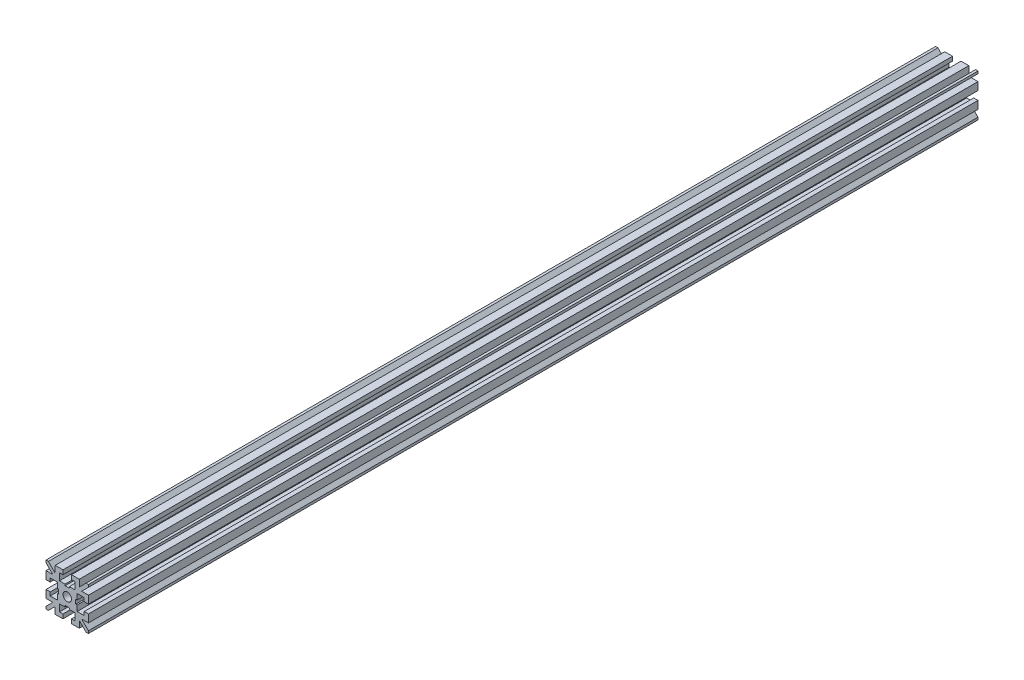
SolidWorks part; units mm, degrees
ref_plane "Front Plane" through (0, 0, 0) normal (0, 0, 1) x (1, 0, 0)
ref_plane "Top Plane" through (0, 0, 0) normal (0, 1, 0) x (1, 0, 0)
ref_plane "Right Plane" through (0, 0, 0) normal (1, 0, 0) x (0, 0, -1)
sketch "Sketch1" plane through (0, 0, 0) normal (0, 0, 1) x (1, 0, 0)
  line L1 (-9.0006, 3.7616) -> (5.9994, 3.7616)
  line L2 (-9.0006, 3.7616) -> (-9.0006, -11.2384)
  line L3 (-9.0006, -11.2384) -> (5.9994, -11.2384)
  line L4 (5.9994, 3.7616) -> (5.9994, -11.2384)
  dimension "D1" = 15
  dimension "D2" = 15
extrude "Boss-Extrude1" add sketch "Sketch1" along normal blind 314.19
sketch "Sketch2" plane through (0, 0, 314.19) normal (0, 0, 1) x (1, 0, 0)
  line L0 (-9.0006, 3.7616) -> (5.9994, -11.2384) construction
  line L1 (5.9994, 3.7616) -> (-9.0006, -11.2384) construction
  line L4 (1.9994, -4.4884) -> (1.9994, -6.4884)
  line L5 (5.9994, -3.7384) -> (1.9994, -3.7384) construction
  line L6 (5.9994, -11.2384) -> (5.9994, 3.7616) construction
  line L7 (-1.5006, 3.7616) -> (-1.5006, -3.7384) construction
  line L8 (5.9994, 3.7616) -> (-9.0006, 3.7616) construction
  line L9 (-9.0006, -3.7384) -> (-1.5006, -3.7384) construction
  line L10 (-9.0006, 3.7616) -> (-9.0006, -11.2384) construction
  line L11 (-1.5006, -11.2384) -> (-1.5006, -3.7384) construction
  line L12 (-9.0006, -11.2384) -> (5.9994, -11.2384) construction
  line L13 (1.9994, -4.4884) -> (1.4994, -4.4884)
  line L14 (1.9994, -0.9884) -> (4.4994, -0.9884)
  line L15 (1.9994, -0.9884) -> (1.9994, -2.9884)
  line L16 (1.9994, -6.4884) -> (4.4994, -6.4884)
  line L17 (4.4994, -0.9884) -> (4.4994, -6.4884)
  line L18 (-4.2506, -7.2384) -> (-4.2506, -9.7384)
  line L19 (1.9994, -2.9884) -> (1.4994, -2.9884)
  line L20 (1.4994, -4.4884) -> (1.4994, -2.9884)
  line L21 (1.4994, -3.7384) -> (-0.0006, -3.7384) construction
  line L22 (-2.2506, -7.2384) -> (-4.2506, -7.2384)
  line L23 (-2.2506, -7.2384) -> (-2.2506, -6.7384)
  line L24 (-2.2506, -6.7384) -> (-0.7506, -6.7384)
  line L25 (-0.7506, -7.2384) -> (-0.7506, -6.7384)
  line L26 (1.2494, -7.2384) -> (-0.7506, -7.2384)
  line L27 (1.2494, -7.2384) -> (1.2494, -9.7384)
  line L28 (1.2494, -9.7384) -> (-4.2506, -9.7384)
  line L29 (-5.0006, -0.9884) -> (-7.5006, -0.9884)
  line L30 (-5.0006, -2.9884) -> (-5.0006, -0.9884)
  line L31 (-5.0006, -2.9884) -> (-4.5006, -2.9884)
  line L32 (-4.5006, -2.9884) -> (-4.5006, -4.4884)
  line L33 (-5.0006, -4.4884) -> (-4.5006, -4.4884)
  line L34 (-5.0006, -6.4884) -> (-5.0006, -4.4884)
  line L35 (-5.0006, -6.4884) -> (-7.5006, -6.4884)
  line L36 (-7.5006, -6.4884) -> (-7.5006, -0.9884)
  line L37 (1.2494, -0.2384) -> (1.2494, 2.2616)
  line L38 (-0.7506, -0.2384) -> (1.2494, -0.2384)
  line L39 (-0.7506, -0.2384) -> (-0.7506, -0.7384)
  line L40 (-0.7506, -0.7384) -> (-2.2506, -0.7384)
  line L41 (-2.2506, -0.2384) -> (-2.2506, -0.7384)
  line L42 (-4.2506, -0.2384) -> (-2.2506, -0.2384)
  line L43 (-4.2506, -0.2384) -> (-4.2506, 2.2616)
  line L44 (-4.2506, 2.2616) -> (1.2494, 2.2616)
  circle A0 centre (-1.5006, -3.7384) radius 1.5
  point P60 (-1.5006, -3.7384)
  dimension "D1" = 5.5
  dimension "D2" = 2.5
  dimension "D3" = 1.5
  dimension "D4" = 2.75
  dimension "D5" = 0.5
  dimension "D6" = 1.5
  dimension "D7" = 0.75
  dimension "D8" = 4
extrude "Cut-Extrude1" cut sketch "Sketch2" against normal up to surface (314.19 mm away) up to face at (-1.5006, -3.7384, 0)
sketch "Sketch3" plane through (0, 0, 314.19) normal (0, 0, 1) x (1, 0, 0)
  line L0 (5.9994, 3.7616) -> (-9.0006, -11.2384) construction
  line L1 (-9.0006, 3.7616) -> (5.9994, -11.2384) construction
  line L2 (5.1509, 3.7616) -> (2.7494, 1.3602)
  line L3 (5.9994, 3.7616) -> (-9.0006, 3.7616) construction
  line L4 (2.7494, 1.3602) -> (2.7494, 3.7616)
  line L5 (2.7494, 3.7616) -> (5.1509, 3.7616)
  line L6 (1.2494, -0.2384) -> (1.2494, 2.2616) construction
  line L7 (5.9994, 0.5116) -> (5.9994, 2.9131)
  line L8 (3.5979, 0.5116) -> (5.9994, 0.5116)
  line L9 (5.9994, 2.9131) -> (3.5979, 0.5116)
  line L10 (1.2494, 2.2616) -> (-4.2506, 2.2616) construction
  line L11 (-3.0006, 3.7616) -> (-0.0006, 3.7616)
  line L12 (-3.0006, 3.7616) -> (-3.0006, 2.2616)
  line L13 (-3.0006, 2.2616) -> (-0.0006, 2.2616)
  line L14 (-0.0006, 3.7616) -> (-0.0006, 2.2616)
  line L15 (-2.2506, -0.7384) -> (-0.7506, -0.7384) construction
  line L16 (2.7494, -8.8369) -> (2.7494, -11.2384)
  line L17 (2.7494, -11.2384) -> (5.1509, -11.2384)
  line L18 (5.1509, -11.2384) -> (2.7494, -8.8369)
  line L19 (5.9994, -10.3898) -> (3.5979, -7.9884)
  line L20 (3.5979, -7.9884) -> (5.9994, -7.9884)
  line L21 (5.9994, -7.9884) -> (5.9994, -10.3898)
  line L22 (5.9994, -5.2384) -> (4.4994, -5.2384)
  line L23 (5.9994, -2.2384) -> (5.9994, -5.2384)
  line L24 (5.9994, -2.2384) -> (4.4994, -2.2384)
  line L25 (4.4994, -2.2384) -> (4.4994, -5.2384)
  line L26 (-6.5991, -7.9884) -> (-9.0006, -7.9884)
  line L27 (-9.0006, -7.9884) -> (-9.0006, -10.3898)
  line L28 (-9.0006, -10.3898) -> (-6.5991, -7.9884)
  line L29 (-8.1521, -11.2384) -> (-5.7506, -8.8369)
  line L30 (-5.7506, -8.8369) -> (-5.7506, -11.2384)
  line L31 (-5.7506, -11.2384) -> (-8.1521, -11.2384)
  line L32 (-3.0006, -11.2384) -> (-3.0006, -9.7384)
  line L33 (-0.0006, -11.2384) -> (-3.0006, -11.2384)
  line L34 (-0.0006, -11.2384) -> (-0.0006, -9.7384)
  line L35 (-0.0006, -9.7384) -> (-3.0006, -9.7384)
  line L36 (-5.7506, 1.3602) -> (-5.7506, 3.7616)
  line L37 (-5.7506, 3.7616) -> (-8.1521, 3.7616)
  line L38 (-8.1521, 3.7616) -> (-5.7506, 1.3602)
  line L39 (-9.0006, 2.9131) -> (-6.5991, 0.5116)
  line L40 (-6.5991, 0.5116) -> (-9.0006, 0.5116)
  line L41 (-9.0006, 0.5116) -> (-9.0006, 2.9131)
  line L42 (-9.0006, -2.2384) -> (-7.5006, -2.2384)
  line L43 (-9.0006, -5.2384) -> (-9.0006, -2.2384)
  line L44 (-9.0006, -5.2384) -> (-7.5006, -5.2384)
  line L45 (-7.5006, -5.2384) -> (-7.5006, -2.2384)
  point P24 (-1.5006, -0.7384)
  point P27 (-1.5006, -3.7384)
  point P61 (-1.5006, -3.7384)
  dimension "D1" = 0.6
  dimension "D2" = 1.5
  dimension "D3" = 3
  dimension "D4" = 1.5
  dimension "D5" = 4
extrude "Cut-Extrude2" cut sketch "Sketch3" against normal up to surface (314.19 mm away) up to face at (-1.5006, 0.2616, 0)
